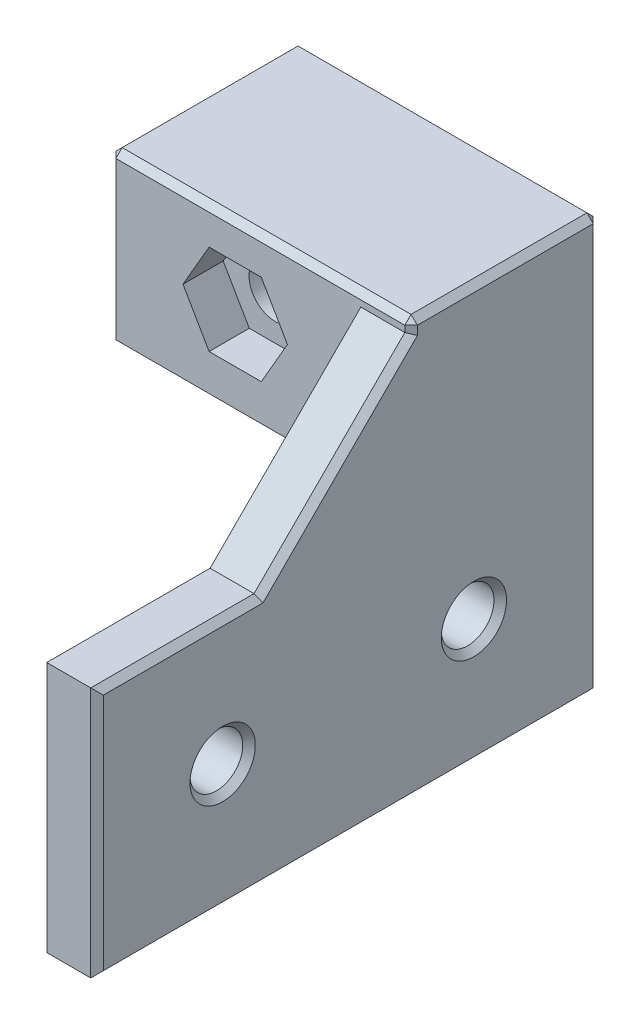
SolidWorks part; units mm, degrees
ref_plane "前视基准面" through (0, 0, 0) normal (0, 0, 1) x (1, 0, 0)
ref_plane "上视基准面" through (0, 0, 0) normal (0, 1, 0) x (1, 0, 0)
ref_plane "右视基准面" through (0, 0, 0) normal (1, 0, 0) x (0, 0, -1)
other "Configuration Table"
sketch "草图1" plane through (0, 0, 0) normal (0, 0, 1) x (1, 0, 0)
  line L0 (0, 0) -> (0, 20) construction
  line L1 (-10, 20) -> (10, 20)
  line L2 (10, 20) -> (10, 0)
  line L3 (10, 0) -> (14, 0)
  line L4 (14, 0) -> (14, 33)
  line L5 (14, 33) -> (-10, 33)
  line L6 (0, 33) -> (0, 20) construction
  line L11 (10, 20) -> (14, 20)
  line L12 (-10, 20) -> (-10, 33)
  dimension "D1" = 20
  dimension "D2" = 20
  dimension "D3" = 13
  dimension "D4" = 4
extrude "凸台-拉伸1" add sketch "草图1" along normal blind 15 contours L1 L11 L4 L5 region at (2, 26.5, 0)
sketch "草图2" plane through (0, 0, 15) normal (0, 0, 1) x (1, 0, 0)
  line L4 (4.1569, 26.5) -> (2.0785, 30.1)
  line L5 (2.0785, 30.1) -> (-2.0785, 30.1)
  line L6 (-2.0785, 30.1) -> (-4.1569, 26.5)
  line L7 (-4.1569, 26.5) -> (-2.0785, 22.9)
  line L8 (-2.0785, 22.9) -> (2.0785, 22.9)
  line L9 (2.0785, 22.9) -> (4.1569, 26.5)
  point P6 (0, 26.5)
  dimension "D1" = 7.2
extrude "切除-拉伸1" cut sketch "草图2" against normal blind 3.2 contours L7 L8 L5 L6 | L8 L9 L4 L5 region at (0, 26.5, 15)
sketch "草图3" plane through (0, 0, 11.8) normal (0, 0, 1) x (1, 0, 0)
  circle A0 centre (0, 26.5) radius 2.1
extrude "切除-拉伸2" cut sketch "草图3" against normal through all
extrude "凸台-拉伸2" add sketch "草图1<4>" along normal blind 40 contours L11 L2 L3 L4 region at (12, 10, 0)
sketch "草图1<4>" plane through (0, 0, 0) normal (0, 0, 1) x (1, 0, 0) same geometry as "草图1"
sketch "草图4" plane through (14, 0, 0) normal (1, 0, 0) x (0, 0, -1)
  line L0 (-40, 10) -> (0, 10) construction
  line L1 (-40, 0) -> (-40, 20) construction
  line L2 (0, 0) -> (0, 33) construction
  circle A0 centre (-30, 10) radius 2.1
  circle A1 centre (-10, 10) radius 2.1
  dimension "D1" = 4.2
  dimension "D2" = 4.2
  dimension "D3" = 10
  dimension "D4" = 10
extrude "切除-拉伸6" cut sketch "草图4" against normal blind 40
chamfer "倒角1" distance 12 angle 45 1 edges at (12, 20, 15)
extrude "切除-拉伸7" cut sketch "草图2<3>" along normal blind 3.2 from offset 15 offset against normal yes
sketch "草图2<3>" plane through (0, 0, 15) normal (0, 0, 1) x (1, 0, 0) same geometry as "草图2"
chamfer "倒角3" distance 0.5 angle 45 15 edges at (-10, 26.5, 15) (-10, 20, 7.5) (-10, 26.5, 0) (2, 33, 15) (-10, 33, 7.5) (2, 33, 0) (14, 0, 20) (14, 10, 40) (14, 20, 33.5) (14, 26, 21) (14, 32.5, 15) (14, 33, 7.5) (14, 16.5, 0) (14, 10, 7.9) (14, 10, 27.9)
